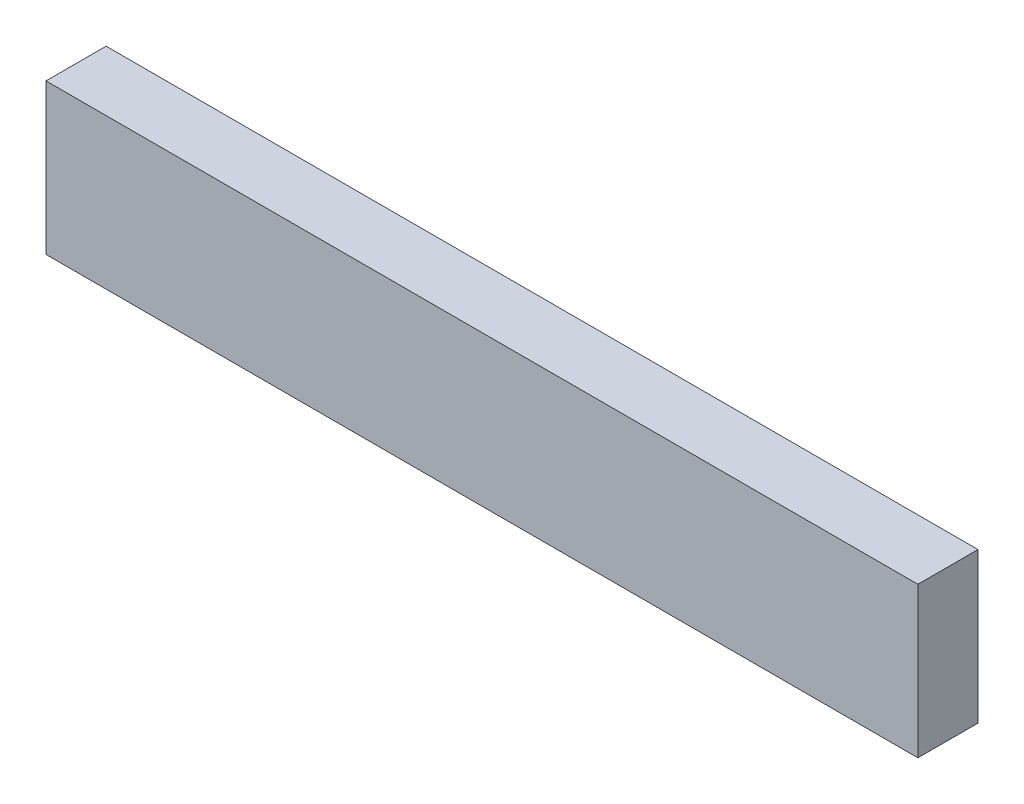
SolidWorks part; units mm, degrees
ref_plane "Front Plane" through (0, 0, 0) normal (0, 0, 1) x (1, 0, 0)
ref_plane "Top Plane" through (0, 0, 0) normal (0, 1, 0) x (1, 0, 0)
ref_plane "Right Plane" through (0, 0, 0) normal (1, 0, 0) x (0, 0, -1)
sketch "Sketch1" plane through (0, 0, 0) normal (0, 1, 0) x (1, 0, 0)
  line L1 (-19.5, 77.5) -> (19.5, 77.5)
  line L2 (-19.5, 77.5) -> (-19.5, -77.5)
  line L3 (-19.5, -77.5) -> (19.5, -77.5)
  line L4 (19.5, 77.5) -> (19.5, -77.5)
  line L5 (-19.5, 77.5) -> (19.5, -77.5) construction
  line L6 (-19.5, -77.5) -> (19.5, 77.5) construction
  point P0 (0, 0)
  dimension "D1" = 39
  dimension "D2" = 155
extrude "Boss-Extrude1" add sketch "Sketch1" along normal blind 2
sketch "Sketch2" plane through (0, 2, 0) normal (0, 1, 0) x (1, 0, 0)
  line L0 (-17.5, -75.5) -> (-17.5, -77.5)
  line L1 (-19.5, 77.5) -> (19.5, 77.5)
  line L2 (-19.5, 77.5) -> (-19.5, -77.5)
  line L3 (-19.5, -77.5) -> (19.5, -77.5)
  line L4 (19.5, 77.5) -> (19.5, -77.5)
  line L5 (-17.5, 75.5) -> (17.5, 75.5)
  line L6 (-17.5, 75.5) -> (-17.5, -75.5)
  line L7 (-17.5, -75.5) -> (17.5, -75.5)
  line L8 (17.5, 75.5) -> (17.5, -75.5)
  line L9 (-17.5, 75.5) -> (17.5, -75.5) construction
  line L10 (-17.5, -75.5) -> (17.5, 75.5) construction
  line L11 (17.5, -75.5) -> (17.5, -77.5)
  point P6 (0, 0)
  line M9 (19.5, -77.5) -> (19.5, 77.5)
  line M10 (19.5, 77.5) -> (-19.5, 77.5)
  line M11 (-19.5, 77.5) -> (-19.5, -77.5)
  line M12 (-19.5, -77.5) -> (19.5, -77.5)
  dimension "D1" = 2
  dimension "D2" = 2
extrude "Boss-Extrude2" add sketch "Sketch2" along normal blind 38 contours L8 L11 L3 L0 L6 L5 M9 M10 M11 M12 region at (-19.0983, 2, 76.5)
sketch "Sketch3" plane through (0, 2, 0) normal (0, 1, 0) x (1, 0, 0)
  line L0 (-17.5, 75.5) -> (-17.5, -77.5) construction
  line L1 (-17.5, -77.5) -> (-15.5, -77.5)
  line L2 (-17.5, -77.5) -> (-17.5, -75.5)
  line L3 (-17.5, -75.5) -> (-15.5, -75.5)
  line L4 (-15.5, -77.5) -> (-15.5, -75.5)
  line L5 (-17.5, -73.3) -> (-15.5, -73.3)
  line L6 (-17.5, -73.3) -> (-17.5, -71.3)
  line L7 (-17.5, -71.3) -> (-15.5, -71.3)
  line L8 (-15.5, -73.3) -> (-15.5, -71.3)
  line L9 (17.5, 75.5) -> (17.5, -77.5) construction
  line L10 (17.5, -77.5) -> (15.5, -77.5)
  line L11 (17.5, -77.5) -> (17.5, -75.5)
  line L12 (17.5, -75.5) -> (15.5, -75.5)
  line L13 (15.5, -77.5) -> (15.5, -75.5)
  line L14 (17.5, -73.3) -> (15.5, -73.3)
  line L15 (17.5, -73.3) -> (17.5, -71.3)
  line L16 (17.5, -71.3) -> (15.5, -71.3)
  line L17 (15.5, -73.3) -> (15.5, -71.3)
  line L18 (15.5, -75.5) -> (15.5, -73.3) construction
  line L19 (-15.5, -73.3) -> (15.5, -73.3) construction
  line L20 (-15.5, -75.5) -> (-15.5, -73.3) construction
  line L21 (-15.5, -75.5) -> (15.5, -75.5) construction
  line L22 (15.5, -71.3) -> (-15.5, -71.3) construction
  dimension "D1" = 2
  dimension "D2" = 2
  dimension "D3" = 2.2
  dimension "D4" = 2
extrude "Boss-Extrude3" add sketch "Sketch3" along normal up to surface (38 mm away) up to face at (0, 40, 0.5)
sketch "Sketch4" plane through (0, 0, -75.5) normal (0, 0, 1) x (1, 0, 0)
  line L0 (-17.5, 40) -> (-15.5, 40)
  line L1 (-17.5, 40) -> (17.5, 40) construction
  line L2 (-15.5, 40) -> (-15.5, 38)
  line L3 (-15.5, 38) -> (-17.5, 38)
  line L5 (-17.5, 38) -> (-17.5, 40)
  line L7 (-17.5, 40) -> (-17.5, 2) construction
  line L8 (-15.5, 33.8) -> (-17.5, 31.8)
  line L9 (-17.5, 31.8) -> (-17.5, 35.8)
  line L10 (-15.5, 33.8) -> (-15.5, 35.8)
  line L11 (-15.5, 35.8) -> (-17.5, 35.8)
  line L12 (0, 0) -> (0, 40) construction
  line L13 (15.5, 35.8) -> (17.5, 35.8)
  line L14 (15.5, 33.8) -> (15.5, 35.8)
  line L15 (17.5, 31.8) -> (17.5, 35.8)
  line L16 (15.5, 33.8) -> (17.5, 31.8)
  line L17 (17.5, 38) -> (17.5, 40)
  line L18 (15.5, 38) -> (17.5, 38)
  line L19 (15.5, 40) -> (15.5, 38)
  line L20 (17.5, 40) -> (15.5, 40)
  dimension "D1" = 2
  dimension "D2" = 2
  dimension "D3" = 45
  dimension "D4" = 2.2
  dimension "D5" = 2
extrude "Boss-Extrude4" add sketch "Sketch4" along normal up to surface (153 mm away) up to face at (0, 20.5, 77.5)
sketch "Sketch5" plane through (0, 2, 0) normal (0, 1, 0) x (1, 0, 0)
  line L1 (-15.5, -77.5) -> (15.5, -77.5)
  line L2 (-15.5, -77.5) -> (-15.5, -75.5)
  line L3 (-15.5, -75.5) -> (15.5, -75.5)
  line L4 (15.5, -77.5) -> (15.5, -75.5)
  line L5 (-15.5, -71.3) -> (15.5, -71.3)
  line L6 (-15.5, -71.3) -> (-15.5, -73.3)
  line L7 (-15.5, -73.3) -> (15.5, -73.3)
  line L8 (15.5, -71.3) -> (15.5, -73.3)
sketch "Sketch6" plane through (0, 0, -75.5) normal (0, 0, 1) x (1, 0, 0)
  line L0 (-17.5, 38) -> (-15.5, 38) construction
  line L1 (-17.5, 38) -> (17.5, 38)
  line L2 (-17.5, 38) -> (-17.5, 35.8)
  line L3 (-17.5, 35.8) -> (17.5, 35.8)
  line L4 (17.5, 38) -> (17.5, 35.8)
  line L5 (-17.5, 38) -> (-17.5, 35.8) construction
  line L6 (-15.5, 35.8) -> (-17.5, 35.8) construction
extrude "Cut-Extrude1" cut sketch "Sketch6" along normal through all
sketch "Sketch7" plane through (0, 2, 0) normal (0, 1, 0) x (1, 0, 0)
  line L1 (-17.5, -75.5) -> (17.5, -75.5)
  line L2 (-17.5, -75.5) -> (-17.5, -73.3)
  line L3 (-17.5, -73.3) -> (17.5, -73.3)
  line L4 (17.5, -75.5) -> (17.5, -73.3)
extrude "Cut-Extrude2" cut sketch "Sketch7" along normal through all
extrude "Boss-Extrude5" add sketch "Sketch5" along normal blind 2
sketch "Sketch8" plane through (0, 0, 0) normal (1, 0, 0) x (0, 0, -1)
  line L0 (75.5, 40) -> (73.5, 40)
  line L1 (-73.3, 40) -> (75.5, 40) construction
  line L2 (73.5, 40) -> (73.5, 38)
  line L3 (-73.3, 38) -> (75.5, 38) construction
  line L4 (73.5, 38) -> (75.5, 38)
  line L5 (75.5, 38) -> (75.5, 40)
  line L6 (75.5, 35.8) -> (73.5, 35.8)
  line L7 (-73.3, 35.8) -> (75.5, 35.8) construction
  line L8 (73.5, 35.8) -> (73.5, 33.8)
  line L9 (-71.3, 33.8) -> (75.5, 33.8) construction
  line L10 (73.5, 33.8) -> (75.5, 31.8)
  line L11 (75.5, 31.8) -> (75.5, 35.8)
  dimension "D1" = 2
extrude "Boss-Extrude6" add sketch "Sketch8" along normal up to surface and the other way up to surface up to face at (17.5, 16.9, -2.1) other way up to face at (-17.5, 16.9, -2.1)
sketch "Sketch10" plane through (-17.5, 0, 0) normal (1, 0, 0) x (0, 0, -1)
  line L1 (-75.5, 35.8) -> (-77.5, 35.8)
  line L2 (-75.5, 35.8) -> (-75.5, 38)
  line L3 (-75.5, 38) -> (-77.5, 38)
  line L4 (-77.5, 35.8) -> (-77.5, 38)
  line L5 (-73.3, 40) -> (-75.5, 40)
  line L6 (-73.3, 40) -> (-73.3, 38)
  line L7 (-73.3, 38) -> (-75.5, 38)
  line L8 (-75.5, 40) -> (-75.5, 38)
  line M1 (-75.5, 40) -> (-75.5, 38)
  line M2 (-75.5, 38) -> (-77.5, 38)
  line M3 (-77.5, 38) -> (-77.5, 35.8)
  line M4 (-77.5, 35.8) -> (-75.5, 35.8)
  line M11 (-73.3, 38) -> (-73.3, 40)
  line M12 (-73.3, 40) -> (-75.5, 40)
extrude "Boss-Extrude8" add sketch "Sketch10" along normal up to surface (2 mm away) contours L2 M4 M2 M3 | L7 M11 M12 M1 region at (-17.5, 39, 74.4) region at (-17.5, 36.9, 76.5) up to face at (-15.5, 39, -0.1)
sketch "Sketch11" plane through (17.5, 0, 0) normal (-1, 0, 0) x (0, 0, 1)
  line L1 (75.5, 35.8) -> (77.5, 35.8)
  line L2 (75.5, 35.8) -> (75.5, 38)
  line L3 (75.5, 38) -> (77.5, 38)
  line L4 (77.5, 35.8) -> (77.5, 38)
  line L5 (73.3, 40) -> (75.5, 40)
  line L6 (73.3, 40) -> (73.3, 38)
  line L7 (73.3, 38) -> (75.5, 38)
  line L8 (75.5, 40) -> (75.5, 38)
  line M2 (75.5, 35.8) -> (77.5, 35.8)
  line M3 (77.5, 35.8) -> (77.5, 38)
  line M4 (77.5, 38) -> (75.5, 38)
  line M5 (75.5, 38) -> (75.5, 40)
  line M6 (75.5, 40) -> (73.3, 40)
  line M7 (73.3, 40) -> (73.3, 38)
extrude "Boss-Extrude9" add sketch "Sketch11" along normal up to surface (2 mm away) contours L2 M2 M3 M4 | L7 M7 M5 M6 region at (17.5, 36.9, 76.5) region at (17.5, 39, 74.4) up to face at (15.5, 39, -0.1)
fillet "Fillet2" radius 2.5 17 edges at (-17.5, 16.9, 71.3) (17.5, 16.9, 71.3) (19.5, 20, 77.5) (-19.5, 20, 77.5) (-19.5, 20, -77.5) (-17.5, 16.9, -75.5) (17.5, 16.9, -75.5) (19.5, 20, -77.5) (-19.5, 40, 0) (0, 40, -77.5) (19.5, 40, 0) (0, 0, -77.5) (0, 0, 77.5) (-19.5, 0, 0) (19.5, 0, 0) (-17.5, 40, 77.5) (17.5, 40, 77.5)
sketch "Sketch13" plane through (0, 0, -77.5) normal (0, 0, -1) x (-1, 0, 0)
  line L0 (15.5, 37.5) -> (15.5, 4) construction
  line L1 (-15.5, 7) -> (15.5, 7)
  line L2 (-15.5, 7) -> (-15.5, 4)
  line L3 (-15.5, 4) -> (15.5, 4)
  line L4 (15.5, 7) -> (15.5, 4)
  dimension "D1" = 3
sketch "Sketch14" plane through (0, 0, -75.5) normal (0, 0, 1) x (1, 0, 0)
  line L1 (-18.25, 9) -> (18.25, 9)
  line L2 (-18.25, 9) -> (-18.25, 1.25)
  line L3 (-18.25, 1.25) -> (18.25, 1.25)
  line L4 (18.25, 9) -> (18.25, 1.25)
  line L5 (15.5, 7) -> (-15.5, 7) construction
  line L7 (17, 0) -> (17, 2.5) construction
  line L8 (19.5, 2.5) -> (17, 2.5) construction
  line L10 (-19.5, 2.5) -> (-17, 2.5) construction
  point P20 (17, 1.25)
  point P23 (18.25, 2.5)
  point P26 (-18.25, 2.5)
  dimension "D1" = 2
extrude "Boss-Extrude10" add sketch "Sketch14" along normal blind 2
extrude "Cut-Extrude4" cut sketch "Sketch13" against normal blind 2
fillet "Fillet3" radius 2 1 edges at (0, 9, -73.5)
fillet "Fillet4" radius 0.5 12 edges at (0, 4, -77.5) (0, 7, -77.5) (15.5, 7, -76.5) (15.5, 4, -76.5) (15.5, 5.5, -77.5) (-15.5, 4, -76.5) (-15.5, 7, -76.5) (-15.5, 5.5, -77.5) (0, 7, -75.5) (-15.5, 5.5, -75.5) (0, 4, -75.5) (15.5, 5.5, -75.5)
sketch "Sketch15" plane through (0, 0, 0) normal (0, -1, 0) x (1, 0, 0)
  line L0 (0, 77.5) -> (0, 0) construction
  line L1 (-17, 77.5) -> (17, 77.5) construction
  line L2 (0, 0) -> (0, -77.5) construction
  line L4 (17, -77.5) -> (-17, -77.5) construction
  circle A0 centre (0, 38.75) radius 5.1
  circle A1 centre (0, -38.75) radius 5.1
  dimension "D1" = 10.2
extrude "Cut-Extrude5" cut sketch "Sketch15" against normal through all
sketch "Sketch16" plane through (0, 2, 0) normal (0, 1, 0) x (1, 0, 0)
  circle A0 centre (0, 38.75) radius 7.1
  circle A1 centre (0, -38.75) radius 7.1
  circle A2 centre (0, 38.75) radius 5.1 construction
  dimension "D1" = 2
extrude "Boss-Extrude11" add sketch "Sketch16" along normal blind 1
fillet "Fillet5" radius 0.5 4 edges at (0, 2, 45.85) (0, 2, -31.65) (0, 3, 45.85) (0, 3, -31.65)
fillet "Fillet7" radius 0.5 8 edges at (15.5, 40, 0.75) (15.5, 39.2678, 76.7678) (-15.5, 40, 0.75) (-15.5, 39.2678, 76.7678) (0, 40, -73.5) (15.5, 20.75, 77.5) (-15.5, 20.75, 77.5) (0, 4, 77.5)
sketch "Sketch17" plane through (0, 0, 0) normal (0, -1, 0) x (1, 0, 0)
  line L0 (-17, -77.5) -> (-17, 70.3)
  line L1 (-17, -77.5) -> (17, -77.5)
  line L2 (17, -77.5) -> (17, 70.3)
  line L3 (17, -75) -> (17, 75) construction
  line L5 (17, 70.3) -> (15, 71.3)
  line L6 (15, 71.3) -> (15, 77.5)
  line L7 (15, 77.5) -> (-15, 77.5)
  line L8 (-15, 77.5) -> (-15, 71.3)
  line L9 (-15, 71.3) -> (-17, 70.3)
  line L10 (-17, 75) -> (-17, -75) construction
  line L12 (-15, 71.3) -> (15, 71.3) construction
  line L13 (17, 70.3) -> (-17, 70.3) construction
  line L14 (0, 71.3) -> (0, 77.5) construction
  line L15 (-17, 77.5) -> (17, 77.5) construction
  arc A0 (-19.5, -75) -> (-17, -77.5) centre (-17, -75) ccw construction
  dimension "D1" = 1
  dimension "D2" = 30
  dimension "D3" = 6.2
extrude "Cut-Extrude6" cut sketch "Sketch17" against normal blind 6
sketch "Sketch18" plane through (0, 0, 0) normal (0, 0, 1) x (1, 0, 0)
  line L0 (15, 9) -> (-15, 9) construction
  line L1 (-14.5, 9) -> (14.5, 9)
  line L2 (-14.5, 9) -> (-14.5, 6)
  line L3 (-14.5, 6) -> (14.5, 6)
  line L4 (14.5, 9) -> (14.5, 6)
  line L5 (-17, 6) -> (17, 6) construction
  line L6 (0, 6) -> (0, 0) construction
  dimension "D1" = 29
extrude "Cut-Extrude8" cut sketch "Sketch18" against normal through all
sketch "Sketch20" plane through (0, 0, 0) normal (0, 0, 1) x (1, 0, 0)
  line L0 (-16, 40) -> (16, 40) construction
  line L1 (-19.5, 40) -> (-14.5, 40)
  line L2 (-19.5, 40) -> (-19.5, 0)
  line L3 (-19.5, 0) -> (-14.5, 0)
  line L4 (-14.5, 40) -> (-14.5, 0)
  line L5 (-14.5, 6) -> (14.5, 6)
  line L6 (-14.5, 6) -> (-14.5, 40)
  line L7 (-14.5, 40) -> (14.5, 40)
  line L8 (14.5, 6) -> (14.5, 40)
  line L9 (14.5, 40) -> (19.5, 40)
  line L10 (14.5, 40) -> (14.5, 0)
  line L11 (14.5, 0) -> (19.5, 0)
  line L12 (19.5, 40) -> (19.5, 0)
  line L13 (-15, 0) -> (-17, 0) construction
  line L14 (-19.5, 2.5) -> (-19.5, 37.5) construction
  line L15 (17, 0) -> (15, 0) construction
  line L16 (19.5, 37.5) -> (19.5, 2.5) construction
extrude "Cut-Extrude11" cut sketch "Sketch20" against normal through all both and the other way through all contours L12 L9 L8 L10 L11 | L1 L2 L3 L4 region at (17, 20, 0)
sketch "Sketch21" plane through (0, 0, -75.5) normal (0, 0, 1) x (1, 0, 0)
  line L1 (-14.5, 31.8) -> (14.5, 31.8)
  line L2 (-14.5, 31.8) -> (-14.5, 40)
  line L3 (-14.5, 40) -> (14.5, 40)
  line L4 (14.5, 31.8) -> (14.5, 40)
  line L5 (14.5, 31.8) -> (-14.5, 31.8)
  line L6 (14.5, 31.8) -> (14.5, 9)
  line L7 (14.5, 9) -> (-14.5, 9)
  line L8 (-14.5, 31.8) -> (-14.5, 9)
extrude "Cut-Extrude12" cut sketch "Sketch21" against normal through all both and the other way through all contours L1 L4 L3 L2 region at (0, 35.9, -75.5)
sketch "Sketch22" plane through (0, 0, -75.5) normal (0, 0, 1) x (1, 0, 0)
  line L0 (14.5, 31.8) -> (14.5, 9) construction
  line L1 (-14.5, 9) -> (14.5, 9)
  line L2 (-14.5, 9) -> (-14.5, 26.8)
  line L3 (-14.5, 26.8) -> (14.5, 26.8)
  line L4 (14.5, 9) -> (14.5, 26.8)
  line L5 (14.5, 31.8) -> (-14.5, 31.8) construction
  dimension "D1" = 5
extrude "Cut-Extrude13" cut sketch "Sketch22" against normal through all
